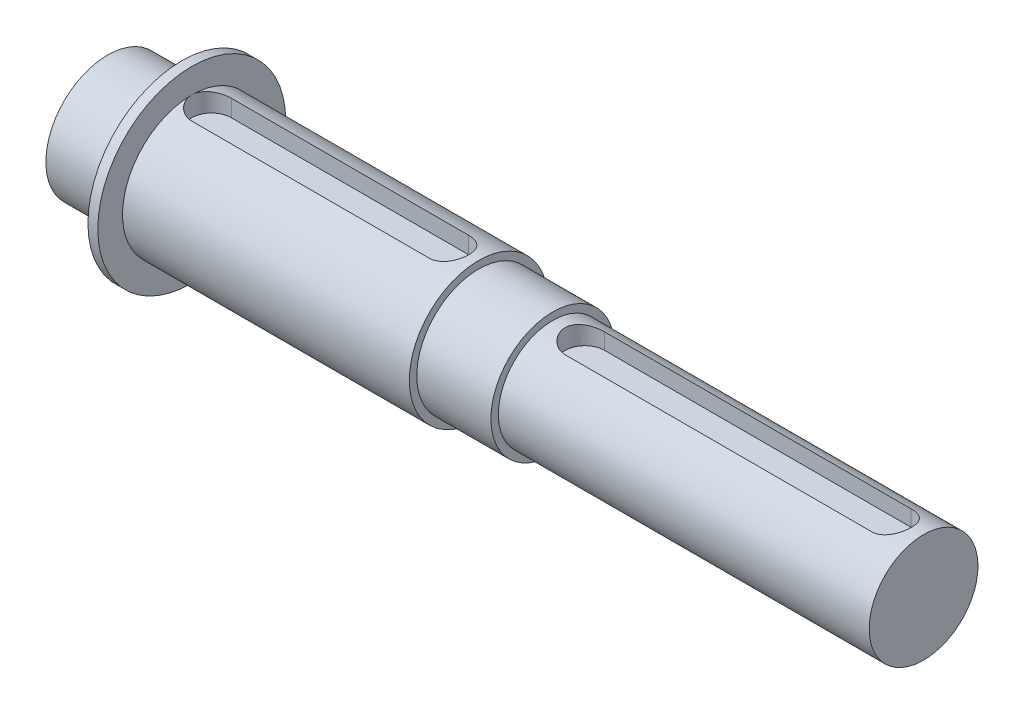
SolidWorks part; units mm, degrees
ref_plane "Спереди" through (0, 0, 0) normal (0, 0, 1) x (1, 0, 0)
ref_plane "Сверху" through (0, 0, 0) normal (0, 1, 0) x (1, 0, 0)
ref_plane "Справа" through (0, 0, 0) normal (1, 0, 0) x (0, 0, -1)
sketch "Эскиз1" plane through (0, 0, 0) normal (0, 0, 1) x (1, 0, 0)
  line L0 (0, 0) -> (0, 12.5)
  line L1 (0, 12.5) -> (15, 12.5)
  line L2 (15, 12.5) -> (15, 14)
  line L3 (15, 14) -> (15, 19)
  line L4 (15, 19) -> (17, 19)
  line L5 (17, 19) -> (17, 14)
  line L6 (17, 14) -> (75, 14)
  line L7 (75, 14) -> (75, 12.5)
  line L8 (75, 12.5) -> (90, 12.5)
  line L9 (90, 12.5) -> (90, 11)
  line L10 (90, 11) -> (165, 11)
  line L11 (165, 11) -> (165, 0)
  line L12 (165, 0) -> (0, 0) construction
  line L13 (0, 0) -> (165, 0)
  dimension "D1" = 25
  dimension "D2" = 28
  dimension "D3" = 22
  dimension "D4" = 25
  dimension "D5" = 15
  dimension "D6" = 60
  dimension "D7" = 75
  dimension "D8" = 165
revolve "Повернуть1" add sketch "Эскиз1" angle 360 about L12
sketch "Эскиз2" plane through (0, 0, 0) normal (0, 1, 0) x (1, 0, 0)
  line L2 (21, 0) -> (69, 0) construction
  line L4 (21, 4) -> (69, 4)
  line L5 (21, -4) -> (69, -4)
  arc A0 (21, 4) -> (21, -4) centre (21, 0) ccw
  arc A1 (69, -4) -> (69, 4) centre (69, 0) ccw
  point P8 (45, 0)
extrude "Вырез-Вытянуть1" cut sketch "Эскиз2" along normal through all from offset 10
sketch "Эскиз3" plane through (0, 0, 0) normal (0, 1, 0) x (1, 0, 0)
  line L2 (96.5, 0) -> (158.5, 0) construction
  line L4 (96.5, 4) -> (158.5, 4)
  line L5 (96.5, -4) -> (158.5, -4)
  arc A0 (96.5, 4) -> (96.5, -4) centre (96.5, 0) ccw
  arc A1 (158.5, -4) -> (158.5, 4) centre (158.5, 0) ccw
  point P8 (127.5, 0)
extrude "Вырез-Вытянуть2" cut sketch "Эскиз3" along normal through all from offset 7 contours L4 A1 L5 A0
